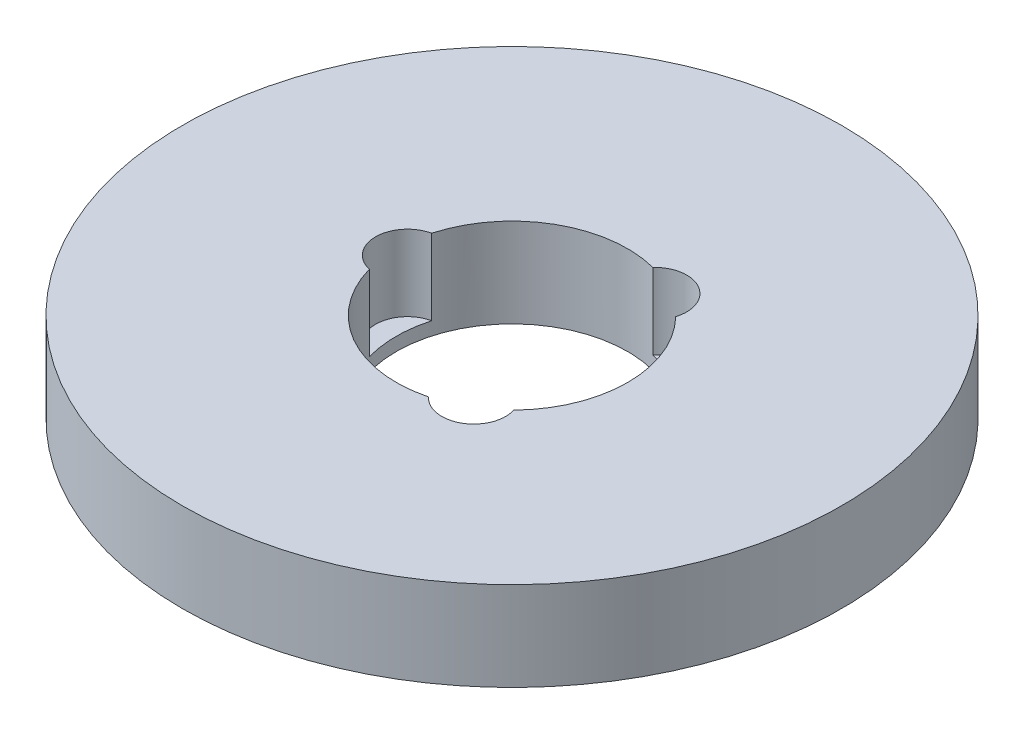
SolidWorks part; units mm, degrees
ref_plane "Front Plane" through (0, 0, 0) normal (0, 0, 1) x (1, 0, 0)
ref_plane "Top Plane" through (0, 0, 0) normal (0, 1, 0) x (1, 0, 0)
ref_plane "Right Plane" through (0, 0, 0) normal (1, 0, 0) x (0, 0, -1)
sketch "Sketch1" plane through (0, 0, 0) normal (0, 1, 0) x (1, 0, 0)
  circle A0 centre (0, 0) radius 92.5
  dimension "FLANGE_OD" = 185
extrude "Boss-Extrude1" add sketch "Sketch1" along normal blind 25
sketch "Sketch2" plane through (0, 0, 0) normal (0, 1, 0) x (1, 0, 0)
  circle A0 centre (0, 0) radius 32.5
  dimension "BORE_D" = 65
extrude "Cut-Extrude1" cut sketch "Sketch2" along normal through all
sketch "Sketch3" plane through (0, 25, 0) normal (0, 1, 0) x (1, 0, 0)
  circle A0 centre (0, 0) radius 29.3231 construction
  circle A1 centre (-29.3231, 0) radius 8.9815
  dimension "BOLT_D" = 17.9631
  dimension "BOLT_PCD" = 58.6461
extrude "Cut-Extrude2" cut sketch "Sketch3" against normal blind 21.2735
pattern_circular "CirPattern1" count 3 over 360 about axis through (0, 0, 0) along (0, 1, 0) of "Cut-Extrude2"
